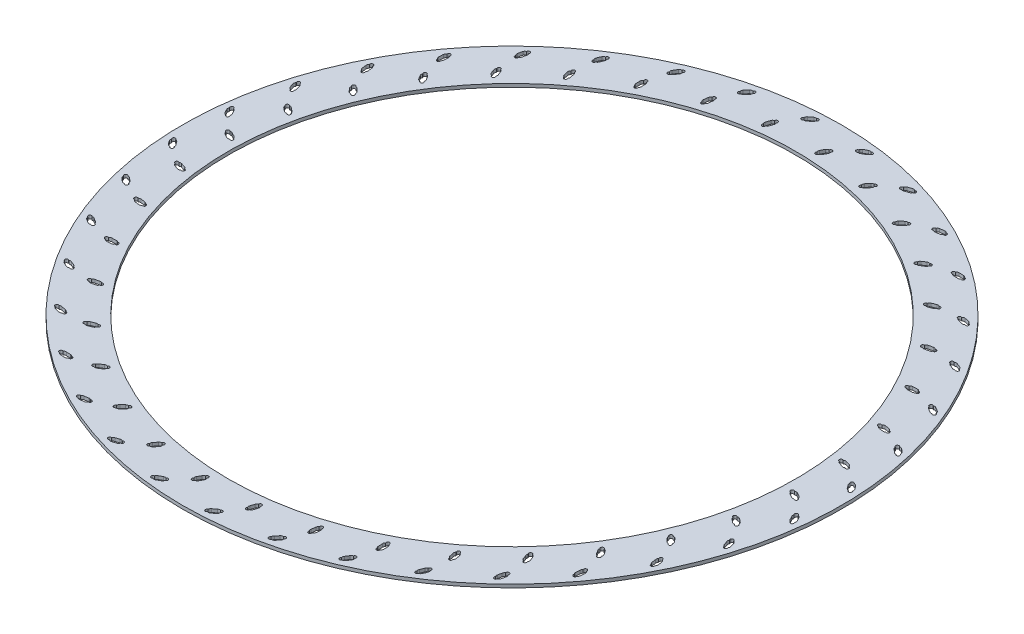
SolidWorks part; units mm, degrees
material "SPCC Steel"
ref_plane "Front Plane" through (0, 0, 0) normal (0, 0, 1) x (1, 0, 0)
ref_plane "Top Plane" through (0, 0, 0) normal (0, 1, 0) x (1, 0, 0)
ref_plane "Right Plane" through (0, 0, 0) normal (1, 0, 0) x (0, 0, -1)
sketch "Sketch1" plane through (0, 0, 0) normal (0, 1, 0) x (1, 0, 0)
  circle A0 centre (0, 0) radius 201.5
  circle A1 centre (0, 0) radius 173.5
  dimension "D1" = 403
  dimension "D2" = 347
sheet metal parameters "Sheet-Metal1" thickness 2 parameters "D1"=1, "厚度"=2
base flange "Base-Flange1" sketch "Sketch1" thickness 2 reverse thickness direction no parameters "D1"=1
sketch "Sketch6" plane through (0, -2, 0) normal (0, -1, 0) x (1, 0, 0)
  arc A0 (177.6125, -22.5885) -> (178.0628, -24.4122) centre (177.5043, -23.5827) ccw construction
  arc A1 (178.0628, -24.4122) -> (179.5951, -24.7654) centre (179.1547, -23.1752) ccw construction
  arc A2 (179.5951, -24.7654) -> (182.296, -23.8862) centre (171.0818, 5.9777) ccw construction
  arc A3 (182.296, -23.8862) -> (183.3269, -22.6987) centre (181.716, -22.3415) ccw construction
  arc A4 (183.3269, -22.6987) -> (182.6174, -20.9595) centre (183.2901, -21.6994) ccw construction
  arc A5 (182.6174, -20.9595) -> (181.1359, -20.7968) centre (181.716, -22.3415) ccw construction
  arc A6 (178.7144, -21.585) -> (181.1359, -20.7968) centre (171.0818, 5.9777) ccw construction
  arc A7 (178.7144, -21.585) -> (177.6125, -22.5885) centre (179.1547, -23.1752) ccw construction
  arc A8 (192.4466, -14.0778) -> (193.8382, -15.3396) centre (192.9117, -14.9631) ccw construction
  arc A9 (193.8382, -15.3396) -> (195.3067, -14.7772) centre (194.0536, -13.7037) ccw construction
  arc A10 (195.3067, -14.7772) -> (197.0568, -12.5401) centre (171.0818, 5.9777) ccw construction
  arc A11 (197.0568, -12.5401) -> (197.2492, -10.9794) centre (195.7133, -11.5823) ccw construction
  arc A12 (197.2492, -10.9794) -> (195.6897, -9.9324) centre (196.6609, -10.1708) ccw construction
  arc A13 (195.6897, -9.9324) -> (194.3698, -10.6244) centre (195.7133, -11.5823) ccw construction
  arc A14 (192.8006, -12.6302) -> (194.3698, -10.6244) centre (171.0818, 5.9777) ccw construction
  arc A15 (192.8006, -12.6302) -> (192.4466, -14.0778) centre (194.0536, -13.7037) ccw construction
  arc A16 (177.6125, -22.5885) -> (178.0628, -24.4122) centre (177.5043, -23.5827) ccw
  arc A17 (178.0628, -24.4122) -> (179.5951, -24.7654) centre (179.1547, -23.1752) ccw
  arc A18 (179.5951, -24.7654) -> (182.296, -23.8862) centre (171.0818, 5.9777) ccw
  arc A19 (182.296, -23.8862) -> (183.3269, -22.6987) centre (181.716, -22.3415) ccw
  arc A20 (183.3269, -22.6987) -> (182.6174, -20.9595) centre (183.2901, -21.6994) ccw
  arc A21 (182.6174, -20.9595) -> (181.1359, -20.7968) centre (181.716, -22.3415) ccw
  arc A22 (178.7144, -21.585) -> (181.1359, -20.7968) centre (171.0818, 5.9777) ccw
  arc A23 (178.7144, -21.585) -> (177.6125, -22.5885) centre (179.1547, -23.1752) ccw
  arc A24 (192.4466, -14.0778) -> (193.8382, -15.3396) centre (192.9117, -14.9631) ccw
  arc A25 (193.8382, -15.3396) -> (195.3067, -14.7772) centre (194.0536, -13.7037) ccw
  arc A26 (195.3067, -14.7772) -> (197.0568, -12.5401) centre (171.0818, 5.9777) ccw
  arc A27 (197.0568, -12.5401) -> (197.2492, -10.9794) centre (195.7133, -11.5823) ccw
  arc A28 (197.2492, -10.9794) -> (195.6897, -9.9324) centre (196.6609, -10.1708) ccw
  arc A29 (195.6897, -9.9324) -> (194.3698, -10.6244) centre (195.7133, -11.5823) ccw
  arc A30 (192.8006, -12.6302) -> (194.3698, -10.6244) centre (171.0818, 5.9777) ccw
  arc A31 (192.8006, -12.6302) -> (192.4466, -14.0778) centre (194.0536, -13.7037) ccw
extrude "Cut-Extrude1" cut sketch "Sketch6" against normal blind 10 normal cut yes
pattern_circular "CirPattern1" count 36 over 360 about axis through (0, -2, 0) along (0, 1, 0) of "Cut-Extrude1"
flat pattern "Flat-Pattern1" [suppressed]
sketch "Sketch3" plane through (0, 0, 0) normal (0, 1, 0) x (1, 0, 0)
sketch3d "Sketch5" [suppressed]
  line L0 (-179.1074, 178.8925, 0) -> (-178.8925, -179.1074, 0) construction
  line L1 (178.8925, 179.1074, 0) -> (179.1074, -178.8925, 0) construction
  line L2 (-179.1074, 178.8925, 0) -> (178.8925, 179.1074, 0) construction
  line L3 (-178.8925, -179.1074, 0) -> (179.1074, -178.8925, 0) construction
